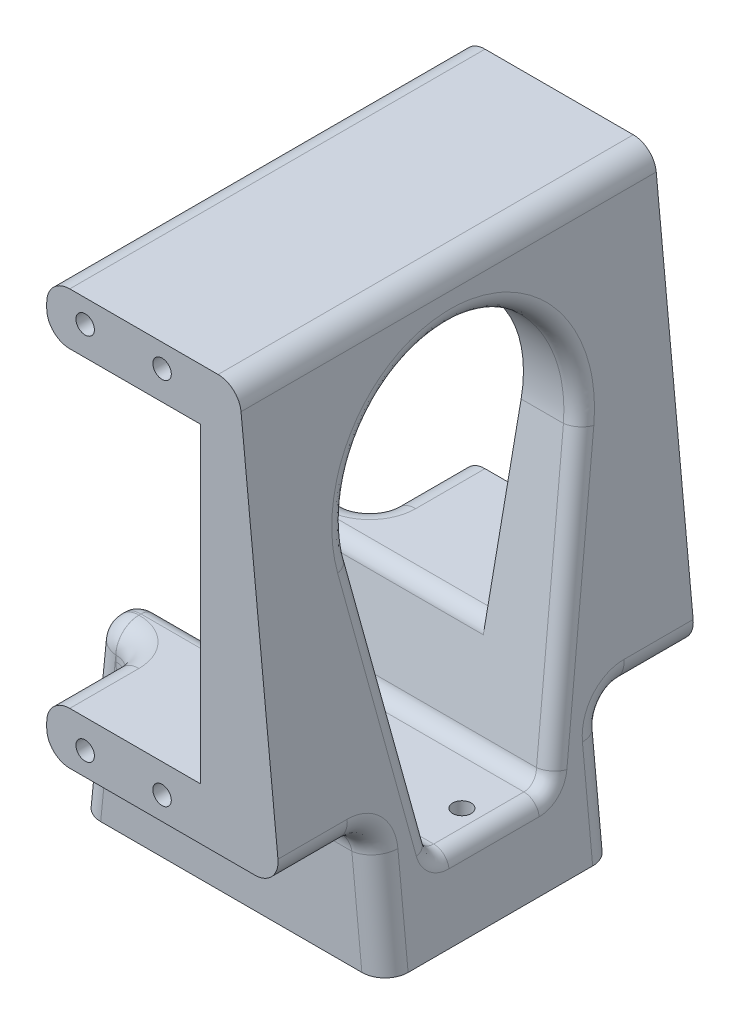
SolidWorks part; units mm, degrees
material "ABS"
ref_plane "Plan de face" through (0, 0, 0) normal (0, 0, 1) x (1, 0, 0)
ref_plane "Plan de dessus" through (0, 0, 0) normal (0, 1, 0) x (1, 0, 0)
ref_plane "Plan de droite" through (0, 0, 0) normal (1, 0, 0) x (0, 0, -1)
sketch "Esquisse1" plane through (0, 0, 0) normal (0, 0, 1) x (1, 0, 0)
  line L0 (-10, 0) -> (0, 0) construction
  line L1 (-10, 27) -> (10, 27)
  line L2 (-10, 27) -> (-10, -27)
  line L3 (-10, -27) -> (10, -27)
  line L4 (10, 27) -> (10, -27)
  line L5 (0, 0) -> (0, 27) construction
  circle A0 centre (-5, 24) radius 1.2
  circle A1 centre (5, 24) radius 1.2
  circle A2 centre (5, -24) radius 1.2
  circle A3 centre (-5, -24) radius 1.2
  dimension "D1" = 48
  dimension "D2" = 10
  dimension "D5" = 2.4
  dimension "D3" = 20
  dimension "D4" = 54
extrude "Boss.-Extru.1" add sketch "Esquisse1" along normal mid plane 54
sketch "Esquisse3" plane through (0, 0, 0) normal (0, 0, 1) x (1, 0, 0)
  line L0 (-10, 27) -> (15, 27)
  line L2 (-10, 27) -> (-10, -20.25)
  line L3 (-18, -43) -> (22, -43)
  line L4 (-18, -43) -> (-15.725, -20.25)
  line L5 (15, 27) -> (22, -43)
  line L7 (-10, -20.25) -> (-15.725, -20.25)
  point P0 (-11, 27)
  dimension "D1" = 43
  dimension "D2" = 40
  dimension "D3" = 15
  dimension "D4" = 18
  dimension "D5" = 5.725
  dimension "D6" = 7
  dimension "D7" = 7
  dimension "D8" = 20.25
extrude "Boss.-Extru.3" add sketch "Esquisse3" along normal mid plane 30
sketch "Esquisse2" plane through (0, 0, 27) normal (0, 0, 1) x (1, 0, 0)
  line L1 (-10, -27) -> (10, -27) construction
  line L2 (10, 27) -> (15, 27)
  line L3 (10, 27) -> (10, -27)
  line L4 (10, -27) -> (20.4, -27)
  line L5 (15, 27) -> (20.4, -27)
  line L6 (22, -43) -> (15, 27) construction
  line L7 (10, 27) -> (-10, 27) construction
  dimension "D1" = 10
extrude "Boss.-Extru.2" add sketch "Esquisse2" against normal up to surface (54 mm away) up to face at (6.2, -24, -27)
sketch "Esquisse8" plane through (0, -43, 0) normal (0, -1, 0) x (1, 0, 0)
  circle A0 centre (-13, 0) radius 1.2
  circle A1 centre (17, 0) radius 1.2
  dimension "D1" = 2.4
  dimension "D2" = 13
  dimension "D3" = 17
extrude "Enlèv. mat.-Extru.4" cut sketch "Esquisse8" against normal blind 20
sketch "Esquisse9" plane through (0, 0, 27) normal (0, 0, 1) x (1, 0, 0)
  line L0 (-10, 27) -> (-10, -27) construction
  line L1 (-10, 20.25) -> (10, 20.25)
  line L2 (-10, 20.25) -> (-10, -20.25)
  line L3 (-10, -20.25) -> (10, -20.25)
  line L4 (10, 20.25) -> (10, -20.25)
  line L5 (0, 0) -> (10, 0) construction
  dimension "D1" = 10
  dimension "D2" = 40.5
extrude "Enlèv. mat.-Extru.5" cut sketch "Esquisse9" against normal through all
fillet "Congé2" radius 3 20 edges at (-10, -27, -21) (-10, -27, 21) (21.2, -35, -15) (21.2, -35, 15) (-10, 20.25, 0) (-10, -20.25, -21) (-10, -20.25, 21) (20.4, -27, -21) (20.4, -27, 21) (15, 27, 0) (-10, 27, 0) (5.2, -27, 15) (5.2, -27, -15) (-12.8625, -20.25, -15) (-16.8625, -31.625, -15) (-12.8625, -20.25, 15) (-16.8625, -31.625, 15) (-15.725, -20.25, 0) (-10, -23.625, -15) (-10, -23.625, 15)
sketch "Esquisse10" plane through (0, 0, 0) normal (-1, 0, 0) x (0, 0, 1)
  line L0 (-5.8671, -33) -> (5.8671, -33)
  line L1 (12, -43) -> (-12, -43) construction
  line L2 (-27, 20.25) -> (27, 20.25) construction
  line L6 (14.6968, 2.2494) -> (7.8267, -31.4001)
  line L7 (-7.8267, -31.4001) -> (-14.6968, 2.2494)
  arc A0 (-7.8267, -31.4001) -> (-5.8671, -33) centre (-5.8671, -31) ccw
  arc A1 (-14.6968, 2.2494) -> (14.6968, 2.2494) centre (0, 5.25) cw
  arc A2 (5.8671, -33) -> (7.8267, -31.4001) centre (5.8671, -31) ccw
  point P5 (0, -33)
  point P16 (-7.5, -33)
  point P17 (7.5, -33)
  dimension "D4" = 15
  dimension "D1" = 2
  dimension "D2" = 11.7342
  dimension "D3" = 10
  dimension "D5" = 15
extrude "Enlèv. mat.-Extru.6" cut sketch "Esquisse10" against normal through all both and the other way through all
fillet "Congé7" radius 2 15 edges at (-1.505, -20.25, -10.1031) (-15.0231, -21.0256, -9.9448) (-16.4176, -27.1758, -8.6891) (-16.9549, -32.5492, -7.132) (-17, -33, 0) (-16.9549, -32.5492, 7.132) (-16.4176, -27.1758, 8.6891) (-15.0231, -21.0256, 9.9448) (-1.505, -20.25, 10.1031) (15.675, 20.25, 0) (19.1575, -14.5754, 11.2617) (20.9549, -32.5492, 7.132) (21, -33, 0) (20.9549, -32.5492, -7.132) (19.1575, -14.5754, -11.2617)
